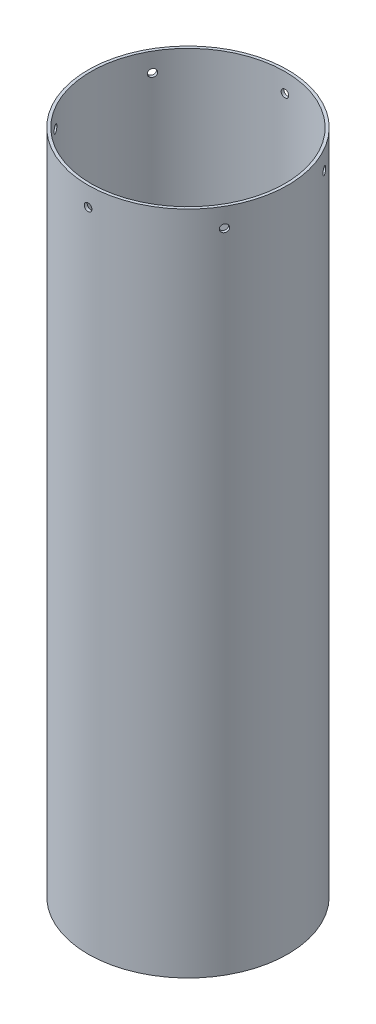
SolidWorks part; units mm, degrees
ref_plane "Спереди" through (0, 0, 0) normal (0, 0, 1) x (1, 0, 0)
ref_plane "Сверху" through (0, 0, 0) normal (0, 1, 0) x (1, 0, 0)
ref_plane "Справа" through (0, 0, 0) normal (1, 0, 0) x (0, 0, -1)
other "Configuration Table"
sketch "Эскиз1" plane through (0, 0, 0) normal (0, 1, 0) x (1, 0, 0)
  circle A0 centre (0, 0) radius 52.5
  circle A1 centre (0, 0) radius 51
  dimension "D1" = 105
  dimension "D2" = 102
extrude "Бобышка-Вытянуть1" add sketch "Эскиз1" along normal blind 350
sketch "Эскиз2" plane through (0, 0, 0) normal (0, 0, 1) x (1, 0, 0)
  line L0 (0, -1000) -> (0, 342) construction
  line L1 (52.5, 350) -> (-52.5, 350) construction
  line L2 (51, 350) -> (-51, 350) construction
  circle A0 centre (0, 340) radius 2
  point P7 (0, 350)
  dimension "D1" = 4
  dimension "D2" = 10
extrude "Вырез-Вытянуть1" cut sketch "Эскиз2" along normal blind 64
pattern_circular "Круговой массив1" count 6 over 360 about axis through (0, 350, 0) along (0, -1, 0) of "Вырез-Вытянуть1"
sketch "Эскиз3" plane through (0, 0, 0) normal (0, 1, 0) x (1, 0, 0)
  line L0 (0, 0) -> (52.5, 0) construction
  line L2 (0, 0) -> (36.0624, -36.0624) construction
  circle A0 centre (0, 0) radius 51 construction
  circle A1 centre (0, 0) radius 52.5 construction
  point P5 (36.0624, -36.0624)
  point P6 (52.5, 0)
  dimension "D1" = 45
ref_plane "Плоскость1" through (0, 0, 0) normal (0.7071, 0, 0.7071) x (0, 1, 0)
